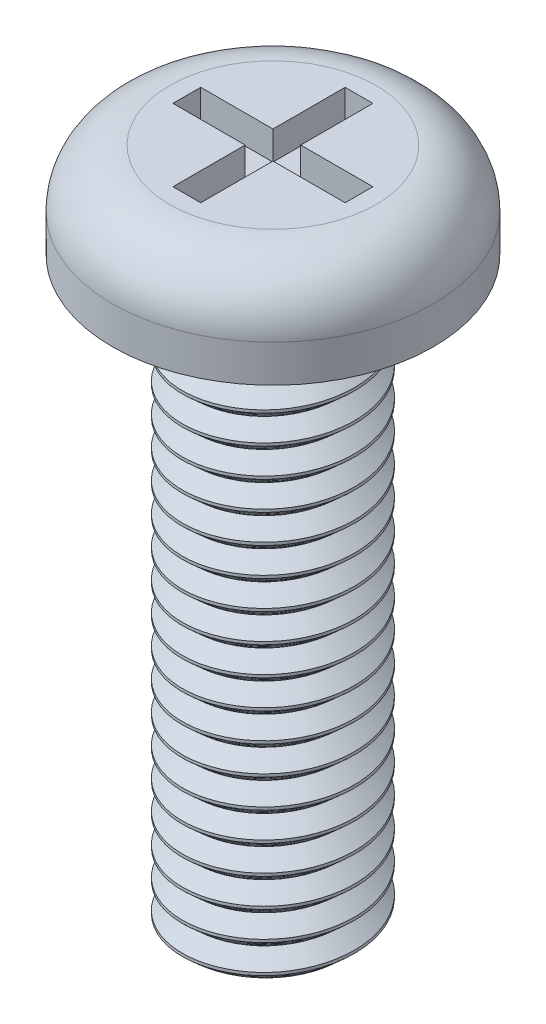
SolidWorks part; units mm, degrees
material "Plain Carbon Steel"
ref_plane "Front Plane" through (0, 0, 0) normal (0, 0, 1) x (1, 0, 0)
ref_plane "Top Plane" through (0, 0, 0) normal (0, 1, 0) x (1, 0, 0)
ref_plane "Right Plane" through (0, 0, 0) normal (1, 0, 0) x (0, 0, -1)
sketch "Sketch1" plane through (0, 0, 0) normal (0, 1, 0) x (1, 0, 0)
  circle A0 centre (0, 0) radius 2.8
  dimension "D1" = 5.6
extrude "Boss-Extrude1" add sketch "Sketch1" along normal blind 1.65 contours A0
sketch "Sketch2" plane through (0, 1.65, 0) normal (0, 1, 0) x (1, 0, 0)
  line L0 (0, -1.502) -> (0, 1.502) construction
  line L1 (1.502, 0) -> (-1.502, 0) construction
  line L2 (-1.502, 0.2423) -> (-1.502, -0.2423)
  line L7 (-1.502, -0.2423) -> (-0.2423, -0.2423)
  line L8 (-0.2423, -0.2423) -> (-0.2423, -1.502)
  line L9 (-0.2423, -1.502) -> (0.2423, -1.502)
  line L10 (0.2423, -1.502) -> (0.2423, -0.2423)
  line L11 (0.2423, -0.2423) -> (1.502, -0.2423)
  line L12 (1.502, -0.2423) -> (1.502, 0.2423)
  line L13 (1.502, 0.2423) -> (0.2423, 0.2423)
  line L14 (0.2423, 0.2423) -> (0.2423, 1.502)
  line L15 (0.2423, 1.502) -> (-0.2423, 1.502)
  line L16 (-0.2423, 1.502) -> (-0.2423, 0.2423)
  line L17 (-0.2423, 0.2423) -> (-1.502, 0.2423)
extrude "Cut-Extrude1" cut sketch "Sketch2" against normal blind 0.5
fillet "Fillet1" radius 1 1 edges at (0, 1.65, 2.8)
sketch "Sketch3" plane through (0, 0, 0) normal (0, 1, 0) x (1, 0, 0)
  circle A0 centre (0, 0) radius 1.5
  dimension "D1" = 3
extrude "Boss-Extrude2" add sketch "Sketch3" against normal blind 10
sketch "Sketch4" plane through (0, 0, 0) normal (0, 0, 1) x (1, 0, 0)
  line L0 (0, 0) -> (0, -10) construction
  line L1 (-1.5, -10) -> (1.5, -10) construction
  line L2 (0, -10) -> (1.25, -10) construction
  line L3 (1.25, -10) -> (1.5, -9.775)
  line L4 (1.5, -10) -> (1.5, 0) construction
  line L5 (1.5, -9.775) -> (1.5, -10.225)
  line L6 (1.5, -10.225) -> (1.25, -10)
  point P5 (1.5, -10)
  dimension "D1" = 0.45
  dimension "D2" = 0.25
sketch "Sketch5" plane through (0, -10, 0) normal (0, -1, 0) x (1, 0, 0)
  circle A0 centre (0, 0) radius 1.5
  circle A1 centre (0, 0) radius 1.5 construction
curve "Helix/Spiral1" pitch 0.5 height 10 radius 1.5 centre (0, -10, 0) axis (0, 1, 0) start towards (1, 0, 0)
sweep "Cut-Sweep1" cut profiles "Sketch4" path "Helix/Spiral1" align with end faces yes
